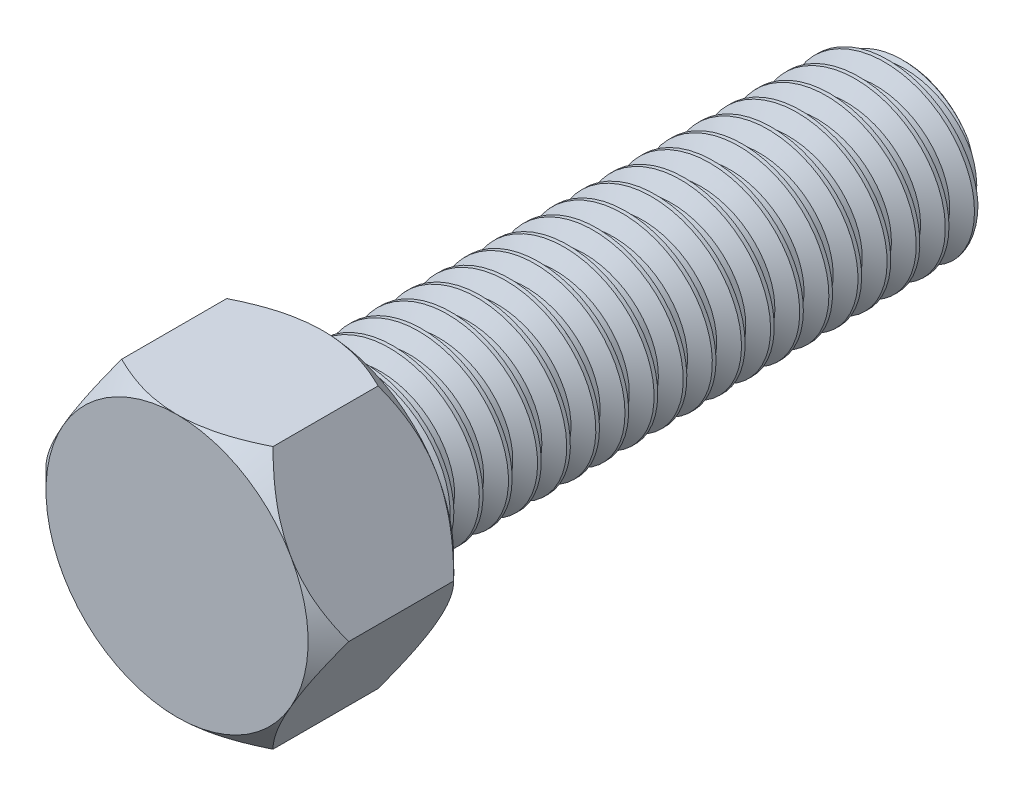
SolidWorks part; units mm, degrees
ref_plane "Front Plane" through (0, 0, 0) normal (0, 0, 1) x (1, 0, 0)
ref_plane "Top Plane" through (0, 0, 0) normal (0, 1, 0) x (1, 0, 0)
ref_plane "Right Plane" through (0, 0, 0) normal (1, 0, 0) x (0, 0, -1)
sketch "Sketch1" plane through (0, 0, 0) normal (0, 0, 1) x (1, 0, 0)
  line L1 (2.5981, 4.5) -> (-2.5981, 4.5)
  line L2 (-2.5981, 4.5) -> (-5.1962, 0)
  line L3 (-5.1962, 0) -> (-2.5981, -4.5)
  line L4 (-2.5981, -4.5) -> (2.5981, -4.5)
  line L5 (2.5981, -4.5) -> (5.1962, 0)
  line L6 (5.1962, 0) -> (2.5981, 4.5)
  circle A1 centre (0, 0) radius 4.5 construction
  dimension "D1" = 9
extrude "Boss-Extrude1" add sketch "Sketch1" along normal mid plane 5
sketch "Sketch2" plane through (0, 0, 2.5) normal (0, 0, 1) x (1, 0, 0)
  circle A0 centre (0, 0) radius 4.5
  dimension "D1" = 9
extrude "Cut-Extrude1" cut sketch "Sketch2" against normal through all draft 45 flip side to cut
mirror "Mirror1" about plane through (0, 0, 0) normal (0, 0, 1) of "Cut-Extrude1"
sketch "Sketch3" plane through (0, 0, -2.5) normal (0, 0, -1) x (-1, 0, 0)
  circle A0 centre (0, 0) radius 3
  dimension "D1" = 6
extrude "Boss-Extrude2" add sketch "Sketch3" along normal blind 20
chamfer "Chamfer1" distance 0.5 angle 45 1 edges at (-3, 0, -22.5)
thread "Thread1" pitch 1 method cut profile "Thread Profile1" start angle 0, offset 0, length 0, pitch 1, diameter 6
ref_plane "Plane1" through (-3, 0, -2.5) normal (0, -1, 0) x (-1, 0, 0)
sketch "Thread Profile1" plane through (-3, 0, -2.5) normal (0, -1, 0) x (-1, 0, 0)
  line L0 (0, 0) -> (0, 1) construction
  line L11 (0, 0) -> (0, 0.875)
  line L12 (0, 0.875) -> (-0.5413, 0.5625)
  line L13 (-0.5413, 0.5625) -> (-0.5413, 0.3125)
  line L15 (-0.5413, 0.3125) -> (0, 0)
  line L17 (-0.5413, 0.4375) -> (0, 0.4375) construction
  point P2 (0, 0)
  dimension "Pitch" = 1
  dimension "Profile_Angle" = 60
  dimension "Profile_Land" = 0.25
  dimension "Profile_Height" = 0.5413
sketch "Sketch8" plane through (0, 0, 0) normal (0, 1, 0) x (1, 0, 0)
  line L0 (0, 0) -> (0, 2.0963) construction
  line L4 (-3, 2.5) -> (-2.4587, 2.8125)
  line L5 (-2.4587, 2.8125) -> (-2.4587, 3.0625)
  line L6 (-2.4587, 3.0625) -> (-3, 3.375)
  line L7 (-3, 3.375) -> (-3, 2.5)
  line L8 (-3, 2.5) -> (-2.4587, 2.8125)
  line L9 (-2.4587, 2.8125) -> (-2.4587, 3.0625)
  line L10 (-2.4587, 3.0625) -> (-3, 3.375)
  line L11 (-3, 3.375) -> (-3, 2.5)
  dimension "D1" = 0
extrude "Cut-Extrude2" cut sketch "Sketch8" against normal through all
